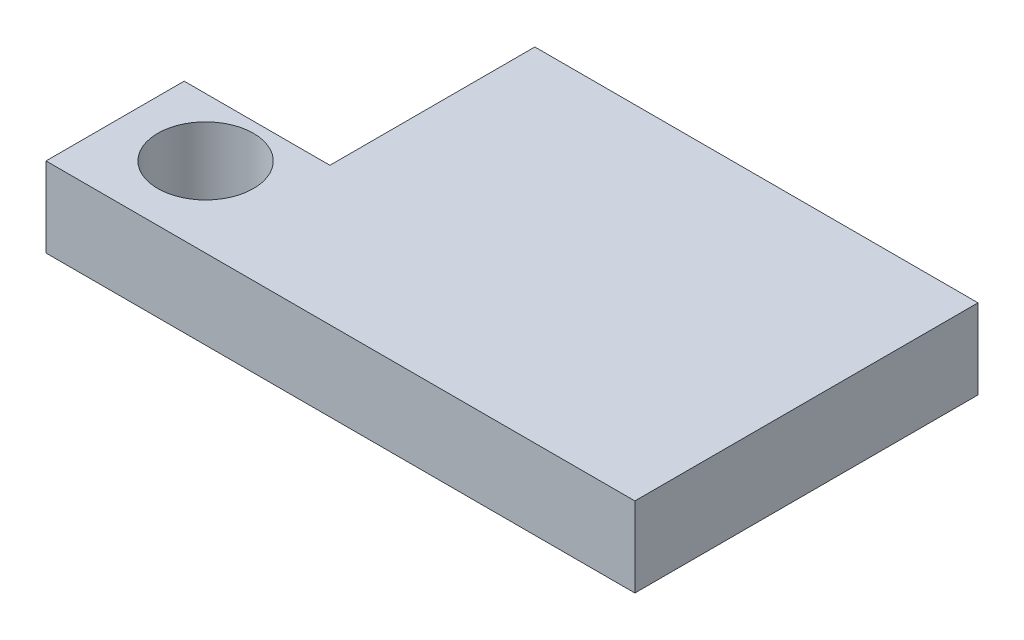
SolidWorks part; units mm, degrees
ref_plane "Front Plane" through (0, 0, 0) normal (0, 0, 1) x (1, 0, 0)
ref_plane "Top Plane" through (0, 0, 0) normal (0, 1, 0) x (1, 0, 0)
ref_plane "Right Plane" through (0, 0, 0) normal (1, 0, 0) x (0, 0, -1)
sketch "Sketch1" plane through (0, 0, 0) normal (0, 0, 1) x (1, 0, 0)
  line L0 (0, 150) -> (0, 0)
  line L1 (0, 150) -> (1106.9725, 150)
  line L3 (0, 0) -> (1106.9725, 0)
  line L4 (1106.9725, 150) -> (1106.9725, 0)
extrude "Boss-Extrude1" add sketch "Sketch1" along normal blind 645 contours L1 L4 L3 L0
sketch "Sketch2" plane through (0, 0, 0) normal (0, -1, 0) x (1, 0, 0)
  line L0 (0, 645) -> (0, 0) construction
  line L1 (0, 645) -> (1106.9725, 645) construction
  circle A0 centre (150, 495) radius 90
  point P2 (144.1361, 522.6438)
  dimension "D1" = 180
  dimension "D2" = 150
  dimension "D3" = 150
extrude "Cut-Extrude1" cut sketch "Sketch2" against normal through all contours A0
sketch "Sketch3" plane through (0, 0, 0) normal (0, -1, 0) x (1, 0, 0)
  line L1 (0, 0) -> (273.9363, 0)
  line L2 (0, 0) -> (0, 385.2587)
  line L3 (0, 385.2587) -> (273.9363, 385.2587)
  line L4 (273.9363, 0) -> (273.9363, 385.2587)
  point P5 (273.9363, 385.2587)
extrude "Cut-Extrude2" cut sketch "Sketch3" against normal through all
